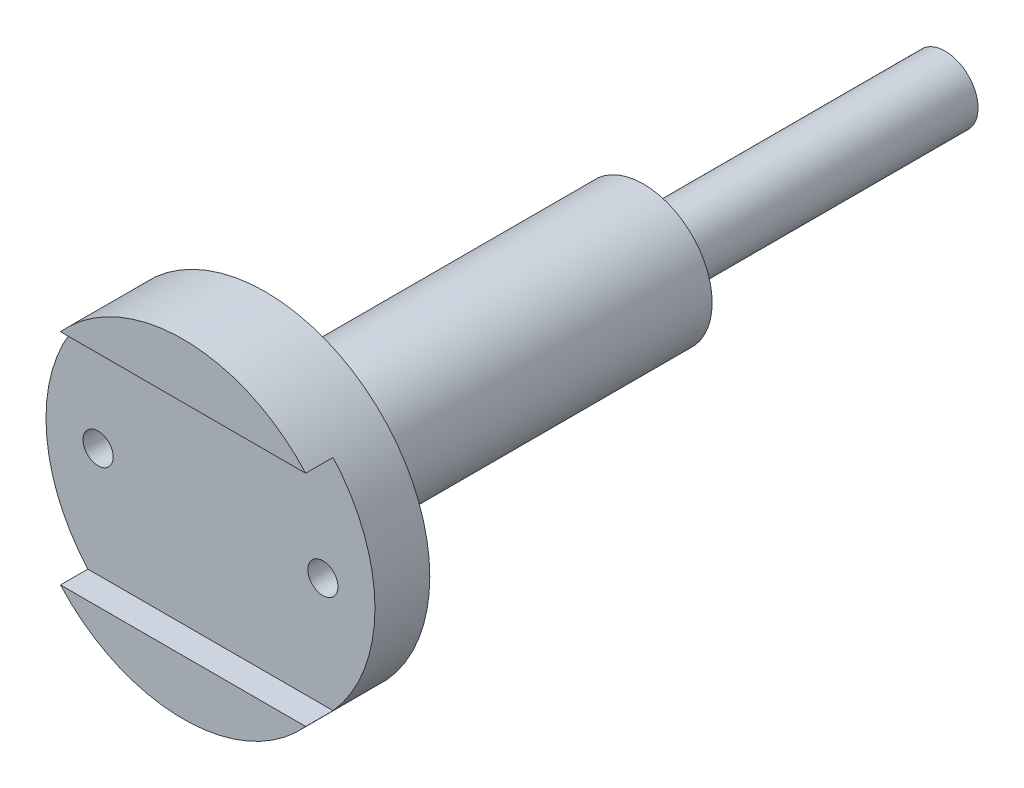
SolidWorks part; units mm, degrees
ref_plane "Plan de face" through (0, 0, 0) normal (0, 0, 1) x (1, 0, 0)
ref_plane "Plan de dessus" through (0, 0, 0) normal (0, 1, 0) x (1, 0, 0)
ref_plane "Plan de droite" through (0, 0, 0) normal (1, 0, 0) x (0, 0, -1)
sketch "Esquisse1" plane through (0, 0, 0) normal (0, 0, 1) x (1, 0, 0)
  circle A0 centre (0, 0) radius 30
  dimension "D1" = 60
extrude "Boss.-Extru.1" add sketch "Esquisse1" along normal blind 15
sketch "Esquisse2" plane through (0, 0, 0) normal (0, 0, -1) x (-1, 0, 0)
  circle A0 centre (0, 0) radius 12.5
  dimension "D1" = 25
extrude "Boss.-Extru.2" add sketch "Esquisse2" along normal blind 69
sketch "Esquisse4" plane through (0, 0, 15) normal (0, 0, 1) x (1, 0, 0)
  line L1 (115, 20) -> (-115, 20)
  line L2 (115, 20) -> (115, -20)
  line L3 (115, -20) -> (-115, -20)
  line L4 (-115, 20) -> (-115, -20)
  line L5 (115, 20) -> (-115, -20) construction
  line L6 (115, -20) -> (-115, 20) construction
  point P0 (0, 0)
  dimension "D1" = 40
  dimension "D2" = 230
extrude "Boss.-Extru.3" [suppressed] add sketch "Esquisse4" along normal blind 5
extrude "Enlèv. mat.-Extru.1" cut sketch "Esquisse4<2>" against normal blind 5
sketch "Esquisse4<2>" plane through (0, 0, 15) normal (0, 0, 1) x (1, 0, 0) same geometry as "Esquisse4"
sketch "Esquisse6" plane through (0, 0, 0) normal (0, 0, -1) x (-1, 0, 0)
  circle A2 centre (0, 0) radius 20.5
  circle A3 centre (0, 0) radius 20.5 construction
  dimension "D1" = 8
hole_wizard "Chambrage pour vis à tête hexagonale M51" positions "Esquisse15" profile "Esquisse14" counterbore size "M5" standard "Ansi Metric" end condition through all
sketch "Esquisse15" plane through (0, 0, 0) normal (0, 0, -1) x (-1, 0, 0)
  circle A0 centre (0, 0) radius 20.5 construction
  point P0 (20.5, 0)
  point P4 (-20.5, 0)
sketch "Esquisse14" plane through (-20.5, 0, 0) normal (1, 0, 0) x (0, 1, 0)
  line L0 (0, 0) -> (0, 15)
  line L1 (0, 15) -> (2.75, 15)
  line L2 (2.75, 3.605) -> (2.75, 15)
  line L3 (2.75, 3.605) -> (2.775, 3.58)
  line L4 (2.775, 3.58) -> (6.12, 3.58)
  line L5 (6.12, 3.58) -> (6.12, 0)
  line L7 (0, 0) -> (6.12, 0)
  line L9 (-2.75, 3.605) -> (-2.775, 3.58) construction
  line L11 (0, -6.35) -> (0, 107.95) construction
  dimension "Diamètre du perçage jusqu'au prochain" = 5.5
  dimension "Profondeur du perçage jusqu'au prochain" = 15
  dimension "Diamètre du chambrage" = 12.24
  dimension "Profondeur du chambrage" = 3.58
  dimension "Diamètre du fraisage milieu" = 5.55
  dimension "Angle du fraisage milieu" = 90
sketch "Esquisse17" plane through (0, 0, -69) normal (0, 0, -1) x (-1, 0, 0)
  circle A0 centre (0, 0) radius 6
  dimension "D1" = 12
extrude "Boss.-Extru.4" add sketch "Esquisse17" along normal blind 55
